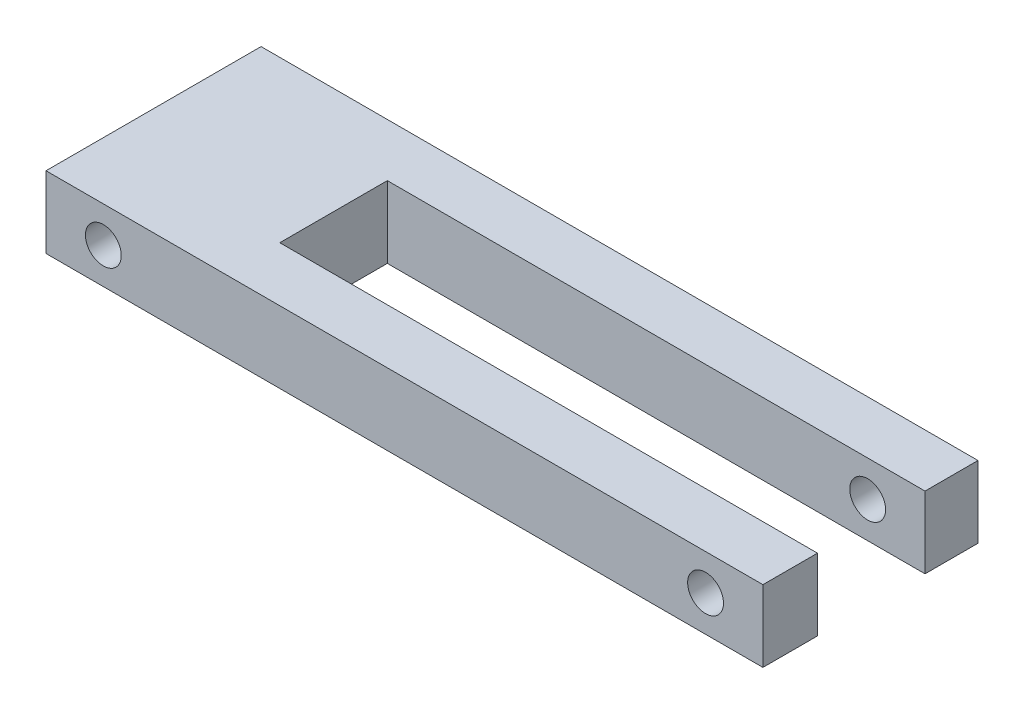
SolidWorks part; units mm, degrees
ref_plane "Front Plane" through (0, 0, 0) normal (0, 0, 1) x (1, 0, 0)
ref_plane "Top Plane" through (0, 0, 0) normal (0, 1, 0) x (1, 0, 0)
ref_plane "Right Plane" through (0, 0, 0) normal (1, 0, 0) x (0, 0, -1)
ref_plane "Plane1" through (0, 0, 0) normal (0, -1, 0) x (-1, 0, 0)
sketch "Base Boundaries" plane through (0, 0, 0) normal (0, -1, 0) x (-1, 0, 0)
  line L0 (0, 0) -> (0, 247.7925) construction
  line L1 (0, 0) -> (0, -252.2075) construction
  line L2 (0, 0) -> (-500, 0) construction
  line L3 (0, 0) -> (500, 0) construction
  line L4 (-500, 0) -> (-500, 247.7925) construction
  line L5 (-500, 247.7925) -> (0, 247.7925) construction
  line L6 (0, 247.7925) -> (500, 247.7925) construction
  line L7 (500, 247.7925) -> (500, 0) construction
  line L8 (500, 0) -> (500, -252.2075) construction
  line L9 (500, -252.2075) -> (0, -252.2075) construction
  line L10 (0, -252.2075) -> (-500, -252.2075) construction
  line L11 (-500, -252.2075) -> (-500, 0) construction
  line L12 (-500, 247.7925) -> (-500, 197.7925) construction
  line L13 (-500, 197.7925) -> (500, 197.7925) construction
  line L14 (500, 197.7925) -> (500, 247.7925) construction
  line L15 (-500, -252.2075) -> (-500, -202.2075) construction
  line L16 (-500, -202.2075) -> (0, -202.2075) construction
  line L17 (0, -202.2075) -> (500, -202.2075) construction
  line L18 (500, -202.2075) -> (500, -252.2075) construction
  line L19 (-500, 247.7925) -> (0, 197.7925) construction
  line L20 (0, 197.7925) -> (500, 247.7925) construction
  line L21 (0, 247.7925) -> (500, 197.7925) construction
  line L22 (0, 247.7925) -> (-500, 197.7925) construction
  line L23 (-500, -252.2075) -> (0, -202.2075) construction
  line L24 (0, -202.2075) -> (500, -252.2075) construction
  line L25 (500, -202.2075) -> (0, -252.2075) construction
  line L26 (0, -252.2075) -> (-500, -202.2075) construction
  line L27 (-500, 197.7925) -> (-500, 147.7925) construction
  line L28 (-500, 147.7925) -> (500, 147.7925) construction
  line L29 (-500, -202.2075) -> (-500, -152.2075) construction
  line L30 (-500, -152.2075) -> (500, -152.2075) construction
  line L31 (500, -152.2075) -> (500, -202.2075) construction
  line L32 (-500, 147.7925) -> (500, 197.7925) construction
  line L33 (500, 147.7925) -> (-500, 197.7925) construction
  line L34 (-500, -202.2075) -> (500, -152.2075) construction
  line L35 (500, -202.2075) -> (-500, -152.2075) construction
  dimension "D1" = 500
  dimension "D2" = 1000
  dimension "D3" = 50
  dimension "D4" = 50
  dimension "D5" = 50
  dimension "D6" = 50
sketch "Wheel Lines" plane through (0, 0, 0) normal (0, -1, 0) x (-1, 0, 0)
  line L0 (-500, 247.7925) -> (-500, 197.7925) construction
  line L1 (-500, 197.7925) -> (-340, 197.7925) construction
  line L2 (-500, 197.7925) -> (500, 197.7925) construction
  line L3 (-340, 197.7925) -> (-340, 247.7925) construction
  line L4 (-500, 247.7925) -> (0, 247.7925) construction
  line L5 (-340, 247.7925) -> (-500, 247.7925) construction
  line L6 (-500, -202.2075) -> (-500, -252.2075) construction
  line L7 (-500, -252.2075) -> (-340, -202.2075) construction
  line L8 (-500, -202.2075) -> (0, -202.2075) construction
  line L9 (-340, -202.2075) -> (-340, -252.2075) construction
  line L10 (0, -252.2075) -> (-500, -252.2075) construction
  line L11 (-340, -252.2075) -> (-500, -202.2075) construction
  line L12 (500, 247.7925) -> (340, 247.7925) construction
  line L13 (0, 247.7925) -> (500, 247.7925) construction
  line L14 (340, 247.7925) -> (500, 197.7925) construction
  line L15 (500, 197.7925) -> (340, 197.7925) construction
  line L16 (340, 197.7925) -> (340, 247.7925) construction
  line L17 (500, -202.2075) -> (340, -202.2075) construction
  line L18 (0, -202.2075) -> (500, -202.2075) construction
  line L19 (340, -202.2075) -> (340, -252.2075) construction
  line L20 (500, -252.2075) -> (0, -252.2075) construction
  line L21 (340, -252.2075) -> (500, -202.2075) construction
  line L22 (500, -202.2075) -> (500, -252.2075) construction
  line L23 (500, -252.2075) -> (340, -202.2075) construction
  line L24 (-340, 247.7925) -> (-500, 197.7925) construction
  line L25 (-500, 247.7925) -> (-340, 197.7925) construction
  line L26 (340, 197.7925) -> (500, 247.7925) construction
  line L27 (420, 222.7925) -> (420, -227.2075) construction
  line L28 (-420, 222.7925) -> (-420, -227.2075) construction
  dimension "D1" = 160
  dimension "D2" = 160
  dimension "D3" = 160
  dimension "D4" = 160
ref_plane "Plane2" through (0, 0, 0) normal (0, -1, 0) x (-1, 0, 0)
sketch "Sketch5" plane through (0, 0, 0) normal (0, -1, 0) x (-1, 0, 0)
  line L0 (-500, 147.7925) -> (500, 147.7925)
  line L1 (500, 147.7925) -> (500, -152.2075)
  line L2 (500, -152.2075) -> (-500, -152.2075)
  line L3 (-500, 0) -> (0, -152.2075) construction
  line L4 (0, 0) -> (-500, -152.2075) construction
  line L5 (-250, -76.1038) -> (-500, -76.1038) construction
  line L6 (-500, -252.2075) -> (-500, 0) construction
  line L7 (-500, -76.1038) -> (500, -76.1038) construction
  line L8 (-500, 147.7925) -> (0, 0) construction
  line L9 (0, 147.7925) -> (-500, 0) construction
  line L10 (-250, 73.8962) -> (-500, 73.8962) construction
  line L11 (-500, 0) -> (-500, 247.7925) construction
  line L12 (-250, 73.8962) -> (500, 73.8962) construction
  line L13 (-500, 147.7925) -> (-500, 73.8962)
  line L14 (0, 147.7925) -> (500, 73.8962) construction
  line L15 (500, 147.7925) -> (0, 73.8962) construction
  line L16 (0, 0) -> (0, 247.7925) construction
  line L17 (250, 110.8444) -> (250, -76.1038) construction
  line L18 (-500, 73.8962) -> (250, 73.8962) construction
  line L19 (250, 73.8962) -> (250, -76.1038) construction
  line L20 (-500, 73.8962) -> (250, 73.8962)
  line L21 (250, 73.8962) -> (250, -76.1038)
  line L22 (250, -76.1038) -> (-500, -76.1038)
  line L23 (-500, -76.1038) -> (-500, -152.2075)
extrude "Boss-Extrude1" add sketch "Sketch5" along normal blind 100
sketch "Sketch6" plane through (0, -100, 0) normal (0, -1, 0) x (-1, 0, 0)
  line L0 (-420, 147.7925) -> (-420, 73.8962) construction
  line L1 (-500, 147.7925) -> (500, 147.7925) construction
  line L2 (-420, 222.7925) -> (-420, -227.2075) construction
  line L3 (-500, 73.8962) -> (250, 73.8962) construction
ref_plane "Plane3" through (0, 0, -147.7925) normal (0, 0, -1) x (-1, 0, 0)
sketch "Sketch8" plane through (0, 0, -147.7925) normal (0, 0, -1) x (-1, 0, 0)
  line L0 (-420, -100) -> (-420, 0) construction
  line L1 (-500, -50) -> (500, -50) construction
  line L3 (-500, -100) -> (-500, 0) construction
  line L4 (500, -100) -> (500, 0) construction
  line L5 (0, -50) -> (0, 0) construction
  line L6 (0, -50) -> (0, -100) construction
  line L7 (500, -100) -> (-500, -100) construction
  circle A0 centre (-420, -50) radius 25
  circle A1 centre (420, -50) radius 25
  dimension "D1" = 50
extrude "Cut-Extrude1" cut sketch "Sketch8" against normal up to surface (300 mm away) contours A0 | A1 up to face at (0, -50, 152.2075)
